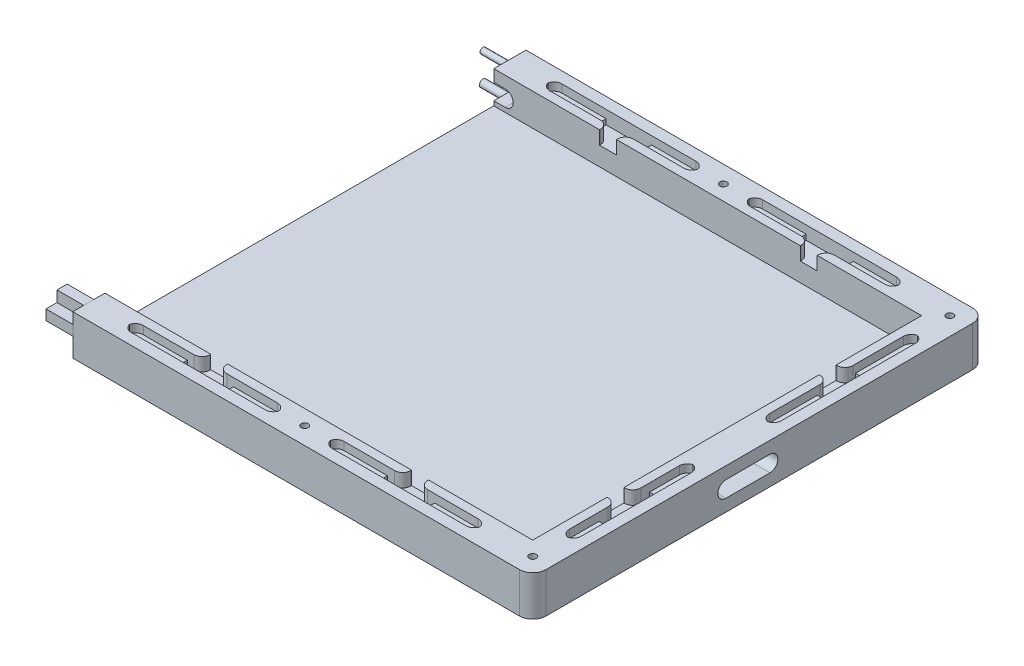
SolidWorks part; units mm, degrees
ref_plane "Front Plane" through (0, 0, 0) normal (0, 0, 1) x (1, 0, 0)
ref_plane "Top Plane" through (0, 0, 0) normal (0, 1, 0) x (1, 0, 0)
ref_plane "Right Plane" through (0, 0, 0) normal (1, 0, 0) x (0, 0, -1)
sketch "Sketch1" plane through (0, 0, 0) normal (0, 1, 0) x (1, 0, 0)
  line L0 (0, 152.7185) -> (0, -149.9342) construction
  line L1 (-90.768, 0) -> (299.0331, 0) construction
  line L2 (0, 72.5) -> (159.54, 72.5)
  line L3 (159.54, 72.5) -> (159.54, -72.5)
  line L4 (159.54, -72.5) -> (0, -72.5)
  line L5 (0, -72.5) -> (0, 72.5)
  dimension "D1" = 159.54
  dimension "D2" = 145
extrude "Boss-Extrude1" add sketch "Sketch1" along normal blind 3
sketch "Sketch3" plane through (0, 0, 0) normal (0, 1, 0) x (1, 0, 0)
  line L0 (0, 105.5814) -> (0, -111.8381) construction
  line L1 (-76.2859, 0) -> (270.0575, 0) construction
  line L2 (0, 72.5) -> (0, 84.5)
  line L3 (0, 84.5) -> (171.54, 84.5)
  line L4 (171.54, 84.5) -> (171.54, -84.5)
  line L5 (171.54, -84.5) -> (0, -84.5)
  line L6 (0, -84.5) -> (0, -72.5)
  line L7 (0, -72.5) -> (159.54, -72.5)
  line L8 (159.54, -72.5) -> (159.54, 72.5)
  line L9 (159.54, 72.5) -> (0, 72.5)
  dimension "D1" = 12
  dimension "D2" = 12
  dimension "D3" = 12
extrude "Boss-Extrude2" add sketch "Sketch3" along normal blind 15
sketch "Sketch4" plane through (0, 15, 0) normal (0, 1, 0) x (1, 0, 0)
  line L0 (45.75, 75.8) -> (45.75, 72.5)
  line L1 (70.6, 75.8) -> (45.75, 75.8)
  line L2 (70.6, 80.3) -> (70.6, 75.8)
  line L3 (14.6, 80.3) -> (70.6, 80.3)
  line L4 (14.6, 75.8) -> (14.6, 80.3)
  line L5 (39.45, 75.8) -> (14.6, 75.8)
  line L6 (39.45, 72.5) -> (39.45, 75.8)
  line L7 (45.75, 72.5) -> (39.45, 72.5)
  line L8 (120.64, 75.8) -> (120.64, 72.5)
  line L9 (145.49, 75.8) -> (120.64, 75.8)
  line L10 (145.49, 80.3) -> (145.49, 75.8)
  line L11 (89.49, 80.3) -> (145.49, 80.3)
  line L12 (89.49, 75.8) -> (89.49, 80.3)
  line L13 (114.34, 75.8) -> (89.49, 75.8)
  line L14 (114.34, 72.5) -> (114.34, 75.8)
  line L15 (120.64, 72.5) -> (114.34, 72.5)
  line L16 (0, 72.5) -> (159.54, 72.5) construction
  line L17 (0, 84.5) -> (0, 72.5) construction
  line L18 (159.54, 72.5) -> (159.54, -72.5) construction
  line L19 (0, 72.5) -> (0, -72.5) construction
  line L20 (145.49, -75.8) -> (120.64, -75.8)
  line L21 (145.49, -80.3) -> (145.49, -75.8)
  line L22 (89.49, -80.3) -> (145.49, -80.3)
  line L23 (89.49, -75.8) -> (89.49, -80.3)
  line L24 (114.34, -75.8) -> (89.49, -75.8)
  line L25 (114.34, -72.5) -> (114.34, -75.8)
  line L26 (120.64, -72.5) -> (114.34, -72.5)
  line L27 (120.64, -75.8) -> (120.64, -72.5)
  line L28 (70.6, -75.8) -> (45.75, -75.8)
  line L29 (70.6, -80.3) -> (70.6, -75.8)
  line L30 (14.6, -80.3) -> (70.6, -80.3)
  line L31 (14.6, -75.8) -> (14.6, -80.3)
  line L32 (39.45, -75.8) -> (14.6, -75.8)
  line L33 (39.45, -72.5) -> (39.45, -75.8)
  line L34 (45.75, -72.5) -> (39.45, -72.5)
  line L35 (45.75, -75.8) -> (45.75, -72.5)
  line L36 (159.54, -72.5) -> (0, -72.5) construction
  line L40 (159.54, -38.5) -> (162.84, -38.5)
  line L49 (159.54, 40.6) -> (162.84, 40.6)
  line L50 (162.84, 40.6) -> (162.84, 65.45)
  line L51 (162.84, 65.45) -> (167.34, 65.45)
  line L52 (167.34, 65.45) -> (167.34, 9.45)
  line L53 (167.34, 9.45) -> (162.84, 9.45)
  line L54 (162.84, 34.3) -> (162.84, 9.45)
  line L55 (159.54, 34.3) -> (162.84, 34.3)
  line L56 (159.54, 40.6) -> (159.54, 34.3)
  line L57 (162.84, -38.5) -> (162.84, -18.15)
  line L58 (162.84, -18.15) -> (167.34, -18.15)
  line L59 (167.34, -18.15) -> (167.34, -65.15)
  line L60 (167.34, -65.15) -> (162.84, -65.15)
  line L61 (162.84, -44.8) -> (162.84, -65.15)
  line L62 (159.54, -44.8) -> (162.84, -44.8)
  line L63 (159.54, -38.5) -> (159.54, -44.8)
  line L64 (0, -72.5) -> (159.54, -72.5) construction
  dimension "D1" = 6.3
  dimension "D2" = 3.3
  dimension "D3" = 4.5
  dimension "D4" = 56
  dimension "D5" = 6.3
  dimension "D6" = 3.3
  dimension "D7" = 4.5
  dimension "D8" = 56
  dimension "D9" = 0
  dimension "D10" = 0
  dimension "D11" = 39.45
  dimension "D12" = 38.9
  dimension "D13" = 56
  dimension "D14" = 39.45
  dimension "D15" = 38.9
  dimension "D16" = 0
  dimension "D17" = 31.9
  dimension "D18" = 6.3
  dimension "D19" = 56
  dimension "D20" = 27.7
  dimension "D21" = 6.3
  dimension "D22" = 47
  dimension "D23" = 56
  dimension "D24" = 3.3
  dimension "D25" = 6.3
  dimension "D26" = 6.3
  dimension "D27" = 3.3
  dimension "D28" = 4.5
  dimension "D29" = 4.5
  dimension "D30" = 3.3
  dimension "D31" = 4.5
  dimension "D32" = 3.3
  dimension "D33" = 4.5
extrude "Cut-Extrude1" cut sketch "Sketch4" against normal blind 3
sketch "Sketch5" plane through (0, 12, 0) normal (0, 1, 0) x (1, 0, 0)
  line L0 (39.45, -75.8) -> (28.5461, -75.8) construction
  line L1 (45.75, -75.8) -> (56.6539, -75.8) construction
  line L2 (39.45, -72.5) -> (39.45, -75.8)
  line L3 (39.45, -75.8) -> (33.9981, -75.8)
  line L4 (33.9981, -75.8) -> (33.9981, -80.3)
  line L5 (33.9981, -80.3) -> (51.2019, -80.3)
  line L6 (51.2019, -80.3) -> (51.2019, -75.8)
  line L7 (45.75, -72.5) -> (39.45, -72.5)
  line L8 (45.75, -72.5) -> (45.75, -75.8)
  line L9 (45.75, -75.8) -> (51.2019, -75.8)
  line L10 (114.34, -75.8) -> (103.0697, -75.8) construction
  line L11 (120.64, -75.8) -> (131.9103, -75.8) construction
  line L12 (114.34, -75.8) -> (108.7049, -75.8)
  line L13 (108.7049, -75.8) -> (108.7049, -80.3)
  line L14 (108.7049, -80.3) -> (126.2751, -80.3)
  line L15 (126.2751, -80.3) -> (126.2751, -75.8)
  line L16 (126.2751, -75.8) -> (120.64, -75.8)
  line L17 (120.64, -75.8) -> (120.64, -72.5)
  line L18 (120.64, -72.5) -> (114.34, -72.5)
  line L19 (114.34, -72.5) -> (114.34, -75.8)
  line L20 (0, -72.5) -> (159.54, -72.5) construction
  line L22 (14.6, -80.3) -> (70.6, -80.3) construction
  line L23 (70.6, -75.8) -> (45.75, -75.8) construction
  line L24 (42.6, -68.4649) -> (42.6, -82.099) construction
  line L26 (89.49, -80.3) -> (145.49, -80.3) construction
  line L27 (114.34, -75.8) -> (89.49, -75.8) construction
  line L28 (117.49, -70.6619) -> (117.49, -81.6393) construction
  line L29 (-14.3619, 0) -> (206.3964, 0) construction
  line L31 (120.64, 72.5) -> (114.34, 72.5)
  line L38 (45.75, 72.5) -> (39.45, 72.5)
  line L48 (159.54, -72.5) -> (159.54, 72.5) construction
  line L49 (159.54, 34.3) -> (162.84, 34.3) construction
  line L56 (162.84, 40.6) -> (159.54, 40.6) construction
  line L59 (157.6179, 36.6875) -> (170.3436, 36.6875) construction
  line L66 (96.0172, 13.3148) -> (96.0172, -25.9889) construction
  line L70 (159.54, -44.8) -> (159.54, -38.5)
  line L75 (159.54, 40.6) -> (162.84, 40.6)
  line L81 (159.54, 34.3) -> (162.84, 34.3)
  line L82 (159.54, 40.6) -> (159.54, 34.3)
  line L94 (158.2993, -40.5875) -> (170.1106, -40.5875) construction
  line L96 (120.64, 72.5) -> (120.64, 75.8)
  line L97 (120.64, 75.8) -> (126.3086, 75.8)
  line L98 (120.64, 75.8) -> (145.49, 75.8) construction
  line L99 (126.3086, 75.8) -> (126.3086, 80.3)
  line L100 (45.75, 72.5) -> (45.75, 75.8)
  line L101 (45.75, 75.8) -> (51.0897, 75.8)
  line L102 (45.75, 75.8) -> (70.6, 75.8) construction
  line L103 (51.0897, 75.8) -> (51.0897, 80.3)
  line L104 (70.6, 80.3) -> (14.6, 80.3) construction
  line L105 (51.0897, 80.3) -> (34.1103, 80.3)
  line L106 (70.6, 80.3) -> (14.6, 80.3) construction
  line L107 (34.1103, 80.3) -> (34.1103, 75.8)
  line L108 (14.6, 75.8) -> (39.45, 75.8) construction
  line L109 (34.1103, 75.8) -> (39.45, 75.8)
  line L110 (39.45, 75.8) -> (39.45, 72.5)
  line L112 (145.49, 80.3) -> (89.49, 80.3) construction
  line L115 (126.3086, 80.3) -> (108.7049, 80.3)
  line L116 (108.7049, 80.3) -> (108.7049, 75.8)
  line L117 (89.49, 75.8) -> (114.34, 75.8) construction
  line L118 (108.7049, 75.8) -> (114.34, 75.8)
  line L119 (114.34, 75.8) -> (114.34, 72.5)
  line L120 (162.84, 40.6) -> (162.84, 44.5797)
  line L121 (162.84, 65.45) -> (162.84, 40.6) construction
  line L122 (162.84, 44.5797) -> (167.34, 44.5797)
  line L123 (167.34, 9.45) -> (167.34, 65.45) construction
  line L124 (167.34, 44.5797) -> (167.34, 30.3203)
  line L125 (167.34, 9.45) -> (167.34, 65.45) construction
  line L126 (167.34, 30.3203) -> (162.84, 30.3203)
  line L127 (162.84, 34.3) -> (162.84, 9.45) construction
  line L128 (162.84, 30.3203) -> (162.84, 34.3)
  line L129 (159.54, -38.5) -> (162.84, -38.5)
  line L130 (162.84, -38.5) -> (162.84, -32.2059)
  line L131 (162.84, -18.15) -> (162.84, -38.5) construction
  line L132 (162.84, -32.2059) -> (167.34, -32.2059)
  line L133 (167.34, -65.15) -> (167.34, -18.15) construction
  line L134 (167.34, -32.2059) -> (167.34, -51.0941)
  line L135 (167.34, -65.15) -> (167.34, -18.15) construction
  line L136 (167.34, -51.0941) -> (162.84, -51.0941)
  line L137 (162.84, -44.8) -> (162.84, -65.15) construction
  line L138 (162.84, -51.0941) -> (162.84, -44.8)
  line L139 (162.84, -44.8) -> (159.54, -44.8)
extrude "Cut-Extrude2" cut sketch "Sketch5" against normal blind 2
sketch "Sketch6" plane through (171.54, 0, 0) normal (1, 0, 0) x (0, 0, -1)
  line L0 (-12.45, 10.5) -> (3.93, 10.5)
  line L1 (-12.45, 4.5) -> (3.93, 4.5)
  line L2 (-15.45, 5.5661) -> (-15.45, 9.4339) construction
  line L5 (-84.5, 7.5) -> (84.5, 7.5) construction
  line L6 (-84.5, 15) -> (-84.5, 0) construction
  line L7 (84.5, 15) -> (84.5, 0) construction
  arc A0 (-12.45, 4.5) -> (-12.45, 10.5) centre (-12.45, 7.5) cw
  arc A1 (3.93, 10.5) -> (3.93, 4.5) centre (3.93, 7.5) cw
  point P6 (-12.45, 10.5)
  point P9 (-15.45, 7.5)
  dimension "D2" = 3
  dimension "D1" = 16.38
  dimension "D3" = 69.05
extrude "Cut-Extrude3" cut sketch "Sketch6" against normal blind 12
sketch "Sketch7" plane through (0, 0, -84.5) normal (0, 0, -1) x (-1, 0, 0)
  line L0 (31.7354, 7.6343) -> (-33.2248, 7.6343) construction
  line L1 (-4.24, 10.6343) -> (12.14, 10.6343)
  line L2 (-4.24, 4.6343) -> (12.14, 4.6343)
  line L3 (-7.24, 4.7002) -> (-7.24, 10.5684) construction
  line L4 (0, 15) -> (0, 0) construction
  line L5 (-171.54, 0) -> (0, 0) construction
  arc A0 (-4.24, 4.6343) -> (-4.24, 10.6343) centre (-4.24, 7.6343) cw
  arc A1 (12.14, 10.6343) -> (12.14, 4.6343) centre (12.14, 7.6343) cw
  point P8 (-4.24, 10.6343)
  point P11 (-7.24, 7.6343)
  dimension "D2" = 3
  dimension "D1" = 16.38
  dimension "D3" = 7.24
  dimension "D4" = 7.6343
extrude "Cut-Extrude4" cut sketch "Sketch7" against normal blind 12
sketch "Sketch8" plane through (0, 0, 0) normal (-1, 0, 0) x (0, 0, 1)
  line L0 (-78.5, 4.6343) -> (-78.5, 0.0234) construction
  line L1 (-72.5, 4.6343) -> (-84.5, 4.6343) construction
  line L2 (-84.5, 12.8171) -> (-72.5, 12.8171) construction
  line L3 (-84.5, 15) -> (-84.5, 10.6343) construction
  line L4 (-72.5, 15) -> (-72.5, 10.6343) construction
  circle A0 centre (-78.5, 12.8171) radius 1.1
  circle A1 centre (-78.5, 2.3288) radius 1.35
  dimension "D1" = 2.2
  dimension "D2" = 2.7
extrude "Boss-Extrude3" add sketch "Sketch8" along normal blind 10
sketch "Sketch9" plane through (0, 0, 0) normal (-1, 0, 0) x (0, 0, 1)
  line L2 (72.5, 9) -> (84.5, 9) construction
  line L3 (72.5, 15) -> (72.5, 3) construction
  line L4 (84.5, 15) -> (84.5, 0) construction
  line L5 (72.5, 3) -> (84.5, 3) construction
  line L6 (78.5, 15) -> (78.5, 3) construction
  line L7 (72.5, 15) -> (84.5, 15) construction
  line L8 (84.4892, 3.011) -> (84.4892, 14.989) construction
  line L9 (84.4892, 14.989) -> (72.5108, 14.989) construction
  line L10 (72.5108, 14.989) -> (72.5117, 3.011) construction
  line L11 (72.5117, 3.011) -> (84.4892, 3.011) construction
  line L12 (84.4892, 3.011) -> (72.5108, 14.989) construction
  line L13 (72.5108, 14.989) -> (84.4892, 14.989) construction
  line L14 (84.4892, 14.989) -> (72.5117, 3.011) construction
  line L15 (78.5, 15.1883) -> (78.5, 3.011) construction
  line L16 (72.5112, 9) -> (83.4994, 9) construction
  line L17 (76.6, 14.989) -> (80.4, 14.989)
  line L18 (84.4892, 7.1) -> (84.4892, 10.9)
  line L19 (80.4, 3.011) -> (76.6, 3.011)
  line L20 (72.5114, 7.1) -> (72.5111, 10.9)
  line L21 (76.6, 14.989) -> (76.6, 10.9)
  line L22 (76.6, 10.9) -> (72.5111, 10.9)
  line L23 (72.5114, 7.1) -> (76.6, 7.1)
  line L24 (76.6, 7.1) -> (76.6, 3.011)
  line L25 (80.4, 3.011) -> (80.4, 7.1)
  line L26 (80.4, 7.1) -> (84.4892, 7.1)
  line L27 (84.4892, 10.9) -> (80.4, 10.9)
  line L28 (80.4, 10.9) -> (80.4, 14.989)
  line L29 (78.5, 9) -> (78.5, 14.989) construction
  line L30 (84.4892, 9) -> (72.5112, 9) construction
  point P26 (78.5, 14.989)
  point P30 (84.4892, 9)
  point P33 (78.5, 3.011)
  point P36 (72.5112, 9)
  point P43 (78.5, 9)
  dimension "D1" = 3.8
  dimension "D2" = 3.8
  dimension "D3" = 3.8
  dimension "D4" = 3.8
  dimension "D5" = 0
extrude "Boss-Extrude5" add sketch "Sketch9" along normal blind 10
fillet "Fillet3" radius 5 1 edges at (171.54, 7.5, 84.5)
fillet "Fillet4" radius 5 1 edges at (171.54, 7.5, -84.5)
sketch "Sketch10" plane through (0, 0, 0) normal (0, -1, 0) x (1, 0, 0)
  circle A0 centre (80.0525, 78.05) radius 1.325
  circle A1 centre (164.8078, 77.7678) radius 1.325
  circle A2 centre (164.8078, -77.7678) radius 1.325
  circle A3 centre (80.0525, -78.05) radius 1.325
  dimension "D1" = 2.65
  dimension "D2" = 2.65
  dimension "D3" = 2.65
  dimension "D4" = 2.65
extrude "Cut-Extrude5" cut sketch "Sketch10" against normal blind 17
sketch "Sketch12" plane through (0, 0, 0) normal (0, -1, 0) x (-1, 0, 0)
  circle A0 centre (-80.0525, -78.05) radius 3
  circle A1 centre (-164.8078, -77.7678) radius 3
  circle A2 centre (-164.8078, 77.7678) radius 3
  circle A3 centre (-80.0525, 78.05) radius 3
  dimension "D1" = 6
  dimension "D2" = 6
  dimension "D3" = 6
  dimension "D4" = 6
extrude "Cut-Extrude6" cut sketch "Sketch12" against normal blind 5
sketch "Sketch13" plane through (0, 0, 0) normal (0, -1, 0) x (1, 0, 0)
  line L0 (80.0525, 78.05) -> (164.8078, 77.7678) construction
  line L1 (122.4301, 77.9089) -> (121.9108, -78.05) construction
  line L2 (80.0525, -64.5) -> (151.54, -64.5) construction
  line L3 (166.54, -84.5) -> (0, -84.5) construction
  line L4 (80.0525, 64.5) -> (151.54, 64.5) construction
  line L5 (0, 84.5) -> (166.54, 84.5) construction
  line L6 (171.54, 79.5) -> (171.54, -79.5) construction
  line L7 (151.54, 64.5) -> (151.54, 84.5) construction
  circle A0 centre (151.54, 64.5) radius 6.25
  circle A1 centre (151.54, -64.5) radius 6.25
  point P18 (151.54, 64.5)
  point P19 (151.54, -64.5)
  dimension "D5" = 12.5
  dimension "D6" = 12.5
  dimension "D1" = 20
  dimension "D2" = 20
  dimension "D3" = 20
  dimension "D4" = 20
extrude "Cut-Extrude7" cut sketch "Sketch13" against normal blind 1
fillet "Fillet5" radius 3 12 edges at (45.75, 12.5, -75.8) (39.45, 12.5, -75.8) (120.64, 12.5, -75.8) (114.34, 12.5, -75.8) (162.84, 12.5, -34.3) (162.84, 12.5, -40.6) (162.84, 12.5, 44.8) (162.84, 12.5, 38.5) (120.64, 12.5, 75.8) (114.34, 12.5, 75.8) (45.75, 12.5, 75.8) (39.45, 12.5, 75.8)
fillet "Fillet6" radius 3 24 edges at (70.6, 13.5, 75.8) (70.6, 13.5, 80.3) (14.6, 13.5, 75.8) (14.6, 13.5, 80.3) (89.49, 13.5, 80.3) (89.49, 13.5, 75.8) (145.49, 13.5, 80.3) (145.49, 13.5, 75.8) (167.34, 13.5, 18.15) (162.84, 13.5, 18.15) (167.34, 13.5, 65.15) (162.84, 13.5, 65.15) (167.34, 13.5, -9.45) (162.84, 13.5, -9.45) (167.34, 13.5, -65.45) (162.84, 13.5, -65.45) (145.49, 13.5, -80.3) (145.49, 13.5, -75.8) (89.49, 13.5, -75.8) (89.49, 13.5, -80.3) (70.6, 13.5, -75.8) (70.6, 13.5, -80.3) (14.6, 13.5, -80.3) (14.6, 13.5, -75.8)
